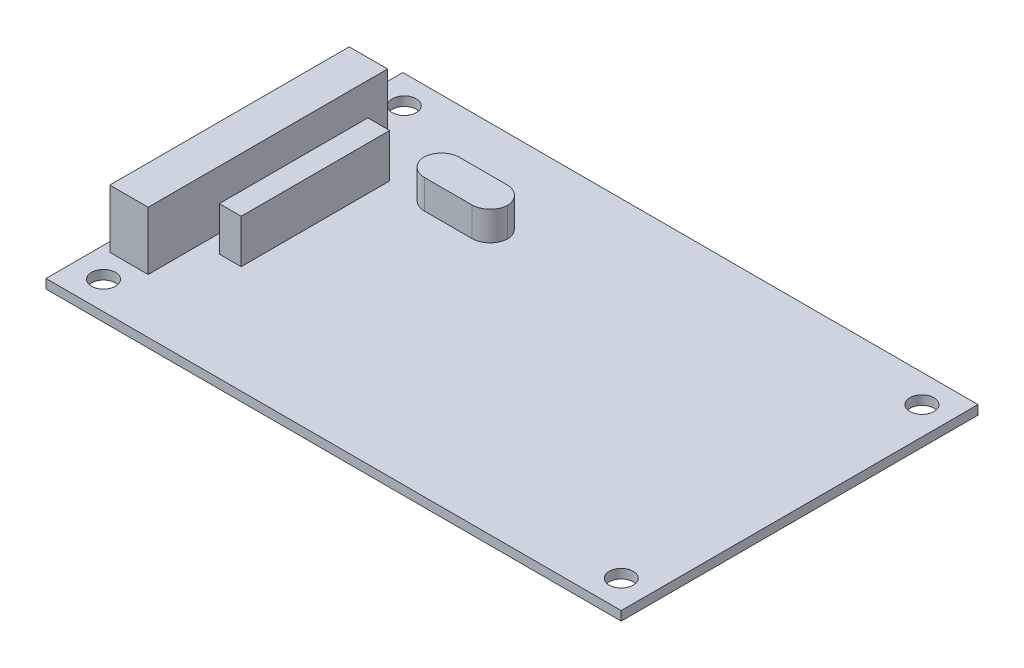
SolidWorks part; units mm, degrees
ref_plane "Front Plane" through (0, 0, 0) normal (0, 0, 1) x (1, 0, 0)
ref_plane "Top Plane" through (0, 0, 0) normal (0, 1, 0) x (1, 0, 0)
ref_plane "Right Plane" through (0, 0, 0) normal (1, 0, 0) x (0, 0, -1)
sketch "Sketch1" plane through (0, 0, 0) normal (0, 1, 0) x (1, 0, 0)
  line L1 (-41.5765, 16.5698) -> (37.4235, 16.5698)
  line L2 (-41.5765, 16.5698) -> (-41.5765, -32.4302)
  line L3 (-41.5765, -32.4302) -> (37.4235, -32.4302)
  line L4 (37.4235, 16.5698) -> (37.4235, -32.4302)
  dimension "D1" = 79
  dimension "D2" = 49
extrude "Boss-Extrude1" add sketch "Sketch1" along normal blind 1.26
sketch "Sketch2" plane through (0, 1.26, 0) normal (0, 1, 0) x (1, 0, 0)
  line L0 (37.4235, -30.2302) -> (-41.5765, -30.2302) construction
  line L1 (37.4235, -32.4302) -> (37.4235, 16.5698) construction
  line L2 (-41.5765, 16.5698) -> (-41.5765, -32.4302) construction
  line L3 (-34.6488, -30.2302) -> (-34.6488, -32.4302) construction
  line L4 (-41.5765, -32.4302) -> (37.4235, -32.4302) construction
  line L5 (-39.1765, 16.5698) -> (-39.1765, -32.4302) construction
  line L6 (37.4235, 16.5698) -> (-41.5765, 16.5698) construction
  line L7 (-39.1765, -7.9302) -> (-41.5765, -7.9302) construction
  line L8 (-41.5765, 14.3698) -> (37.4235, 14.3698) construction
  line L9 (-2.0765, 14.3698) -> (-2.0765, 16.5698) construction
  line L10 (35.2235, 16.5698) -> (35.2235, -32.4302) construction
  line L11 (35.2235, -7.9302) -> (37.4235, -7.9302) construction
  circle A0 centre (33.5735, 12.7198) radius 1.65
  circle A1 centre (33.5735, -28.5802) radius 1.65
  circle A2 centre (-37.5265, -28.5802) radius 1.65
  circle A3 centre (-37.5265, 12.7198) radius 1.65
  dimension "D5" = 3.3
  dimension "D1" = 2.2
  dimension "D2" = 2.4
  dimension "D3" = 2.2
  dimension "D4" = 2.2
extrude "Cut-Extrude1" cut sketch "Sketch2" against normal blind 1.26
sketch "Sketch3" plane through (0, 1.26, 0) normal (0, 1, 0) x (1, 0, 0)
  line L0 (-40.3065, -8.5002) -> (-41.5765, -8.5002) construction
  line L1 (-35.0365, 7.9398) -> (-40.3065, 7.9398)
  line L2 (-35.0365, 7.9398) -> (-35.0365, -24.9402)
  line L3 (-35.0365, -24.9402) -> (-40.3065, -24.9402)
  line L4 (-40.3065, 7.9398) -> (-40.3065, -24.9402)
  line L5 (-41.5765, 16.5698) -> (-41.5765, -32.4302) construction
  line L6 (-35.0365, 7.9398) -> (-35.0365, 16.5698) construction
  line L7 (37.4235, 16.5698) -> (-41.5765, 16.5698) construction
  line L8 (-35.0365, -24.9402) -> (-35.0365, -32.4302) construction
  line L9 (-41.5765, -32.4302) -> (37.4235, -32.4302) construction
  line L10 (-35.0365, -14.4993) -> (-41.5765, -14.4993) construction
  dimension "D1" = 1.27
  dimension "D2" = 7.49
  dimension "D3" = 8.63
  dimension "D4" = 6.54
extrude "Boss-Extrude2" add sketch "Sketch3" along normal blind 8
sketch "Sketch4" plane through (0, 1.26, 0) normal (0, 1, 0) x (1, 0, 0)
  line L0 (-29.5765, -17.6302) -> (-29.5765, -32.4302) construction
  line L1 (-29.5765, -17.6302) -> (-32.5765, -17.6302)
  line L2 (-29.5765, -17.6302) -> (-29.5765, 2.7698)
  line L3 (-29.5765, 2.7698) -> (-32.5765, 2.7698)
  line L4 (-32.5765, -17.6302) -> (-32.5765, 2.7698)
  line L5 (-41.5765, -32.4302) -> (37.4235, -32.4302) construction
  line L6 (-29.5765, 2.7698) -> (-29.5765, 16.5698) construction
  line L7 (37.4235, 16.5698) -> (-41.5765, 16.5698) construction
  line L8 (-29.5765, 1.2825) -> (-41.5765, 1.2825) construction
  line L9 (-41.5765, 16.5698) -> (-41.5765, -32.4302) construction
  line L10 (-32.5765, -18.074) -> (-41.5765, -18.074) construction
  dimension "D1" = 14.8
  dimension "D2" = 13.8
  dimension "D3" = 12
  dimension "D4" = 9
extrude "Boss-Extrude3" add sketch "Sketch4" along normal blind 6
sketch "Sketch5" plane through (0, 1.26, 0) normal (0, 1, 0) x (1, 0, 0)
  line L0 (-14.5765, 3.9698) -> (37.4235, 3.9698) construction
  line L1 (-14.5765, 6.3698) -> (-26.0765, 6.3698)
  line L2 (-14.5765, 6.3698) -> (-14.5765, 1.5698)
  line L3 (-14.5765, 1.5698) -> (-26.0765, 1.5698)
  line L4 (-26.0765, 6.3698) -> (-26.0765, 1.5698)
  line L5 (37.4235, -32.4302) -> (37.4235, 16.5698) construction
  line L6 (-26.0765, 3.9698) -> (-41.5765, 3.9698) construction
  line L7 (-41.5765, 16.5698) -> (-41.5765, -32.4302) construction
  line L8 (-20.3265, 6.3698) -> (-20.3265, 16.5698) construction
  line L9 (37.4235, 16.5698) -> (-41.5765, 16.5698) construction
  line L10 (-20.3265, 1.5698) -> (-20.3265, -32.4302) construction
  line L11 (-41.5765, -32.4302) -> (37.4235, -32.4302) construction
  dimension "D1" = 10.2
  dimension "D2" = 34
  dimension "D3" = 15.5
  dimension "D4" = 52
extrude "Boss-Extrude4" add sketch "Sketch5" along normal blind 4
fillet "Fillet1" radius 2.5 4 edges at (-26.0765, 3.26, -6.3698) (-26.0765, 3.26, -1.5698) (-14.5765, 3.26, -1.5698) (-14.5765, 3.26, -6.3698)
